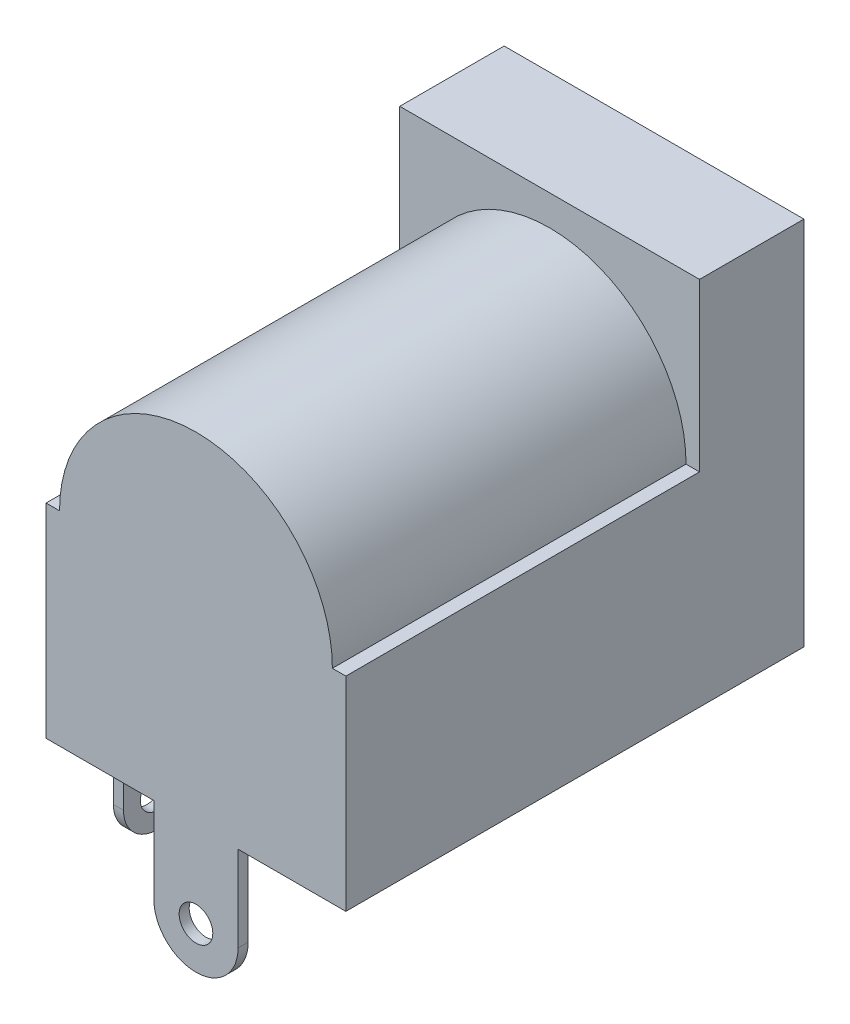
SolidWorks part; units mm, degrees
ref_plane "Plano frontal" through (0, 0, 0) normal (0, 0, 1) x (1, 0, 0)
ref_plane "Plano superior" through (0, 0, 0) normal (0, 1, 0) x (1, 0, 0)
ref_plane "Plano direito" through (0, 0, 0) normal (1, 0, 0) x (0, 0, -1)
sketch "Esboço1" plane through (0, 0, 0) normal (0, 0, 1) x (1, 0, 0)
  line L1 (-4.45, 5.5) -> (4.45, 5.5)
  line L2 (-4.45, 5.5) -> (-4.45, -5.5)
  line L3 (-4.45, -5.5) -> (4.45, -5.5)
  line L4 (4.45, 5.5) -> (4.45, -5.5)
  line L5 (-4.45, 5.5) -> (4.45, -5.5) construction
  line L6 (-4.45, -5.5) -> (4.45, 5.5) construction
  point P0 (0, 0)
  dimension "D1" = 8.9
  dimension "D2" = 11
extrude "Ressalto-extrusão1" add sketch "Esboço1" along normal blind 13.6
sketch "Esboço2" plane through (0, 0, 13.6) normal (0, 0, 1) x (1, 0, 0)
  line L0 (-4.45, 5.5) -> (-4.45, -5.5) construction
  line L1 (4.45, -5.5) -> (4.45, 5.5) construction
  line L3 (-4.45, 0.55) -> (-4.45, 5.5)
  line L4 (-4.45, 5.5) -> (4.45, 5.5)
  line L5 (4.45, 5.5) -> (4.45, 0.55)
  line L6 (-4.45, 0.55) -> (-4.05, 0.55)
  line L7 (4.45, 0.55) -> (4.05, 0.55)
  arc A1 (-4.05, 0.55) -> (4.05, 0.55) centre (0, 0.55) cw
  dimension "D1" = 0.4
  dimension "D3" = 4.05
  dimension "D2" = 0.4
  dimension "D4" = 4.95
extrude "Corte-extrusão1" cut sketch "Esboço2" against normal blind 10.5
sketch "Esboço3" plane through (0, 0, 0) normal (0, 0, -1) x (-1, 0, 0)
  line L0 (-4.45, 5.5) -> (4.45, 5.5) construction
  line L1 (-4.45, -5.5) -> (-4.45, 5.5) construction
  circle A0 centre (0, 1) radius 3.15
  dimension "D1" = 6.3
  dimension "D2" = 4.5
  dimension "D3" = 4.45
extrude "Corte-extrusão2" cut sketch "Esboço3" against normal blind 9.5
sketch "Esboço4" plane through (0, 0, 9.5) normal (0, 0, -1) x (-1, 0, 0)
  circle A0 centre (0, 1) radius 1.25
  dimension "D1" = 2.5
extrude "Ressalto-extrusão2" add sketch "Esboço4" along normal blind 8
fillet "Filete1" radius 0.5 1 edges at (-1.25, 1, 1.5) second distance 1 first distance on face at (-1.25, 1, 1.5)
sketch "Esboço5" plane through (0, -5.5, 0) normal (0, -1, 0) x (1, 0, 0)
  line L0 (-4.45, 13.6) -> (4.45, 13.6) construction
  line L1 (-1.25, 13.6) -> (1.25, 13.6)
  line L2 (-1.25, 13.6) -> (-1.25, 13.3)
  line L3 (-1.25, 13.3) -> (1.25, 13.3)
  line L4 (1.25, 13.6) -> (1.25, 13.3)
  line L5 (4.45, 13.6) -> (4.45, 0) construction
  line L6 (-1.25, 7.3) -> (1.25, 7.3)
  line L7 (-1.25, 7.3) -> (-1.25, 7)
  line L8 (-1.25, 7) -> (1.25, 7)
  line L9 (1.25, 7.3) -> (1.25, 7)
  dimension "D1" = 2.5
  dimension "D2" = 0.3
  dimension "D3" = 0.3
  dimension "D4" = 2.5
  dimension "D5" = 6
  dimension "D6" = 3.2
  dimension "D7" = 3.2
extrude "Ressalto-extrusão3" add sketch "Esboço5" along normal blind 3.8
sketch "Esboço7" plane through (0, 0, 13.6) normal (0, 0, 1) x (1, 0, 0)
  line L0 (-1.25, -9.3) -> (-1.25, -5.5) construction
  line L1 (1.25, -9.3) -> (1.25, -5.5) construction
  line L2 (1.25, -9.3) -> (-1.25, -9.3) construction
  line L3 (-1.25, -8.04) -> (-1.25, -9.3)
  line L4 (-1.25, -9.3) -> (1.25, -9.3)
  line L5 (1.25, -9.3) -> (1.25, -8.04)
  arc A0 (-1.25, -8.04) -> (1.25, -8.04) centre (0, -8.04) ccw
  dimension "D1" = 1.25
  dimension "D2" = 1.26
extrude "Corte-extrusão3" cut sketch "Esboço7" against normal blind 10
sketch "Esboço8" plane through (0, 0, 13.6) normal (0, 0, 1) x (1, 0, 0)
  circle A0 centre (0, -8.04) radius 0.5
  dimension "D1" = 1
extrude "Corte-extrusão4" cut sketch "Esboço8" against normal blind 10
sketch "Esboço9" plane through (-4.45, 0, 0) normal (-1, 0, 0) x (0, 0, 1)
  line L0 (13.6, -5.5) -> (0, -5.5) construction
  line L1 (9.3, -1.5) -> (11.3, -1.5)
  line L2 (9.3, -1.5) -> (9.3, -8.5)
  line L4 (11.3, -1.5) -> (11.3, -8.5)
  line L5 (13.6, 0.55) -> (13.6, -5.5) construction
  arc A0 (9.3, -8.5) -> (11.3, -8.5) centre (10.3, -8.5) ccw
  dimension "D1" = 2
  dimension "D2" = 7
  dimension "D3" = 3
  dimension "D4" = 2.3
extrude "Ressalto-extrusão4" add sketch "Esboço9" along normal blind 0.3
sketch "Esboço10" plane through (-4.75, 0, 0) normal (-1, 0, 0) x (0, 0, 1)
  circle A0 centre (10.3, -8.5) radius 0.5
  dimension "D1" = 1
extrude "Corte-extrusão5" cut sketch "Esboço10" against normal blind 0.3
